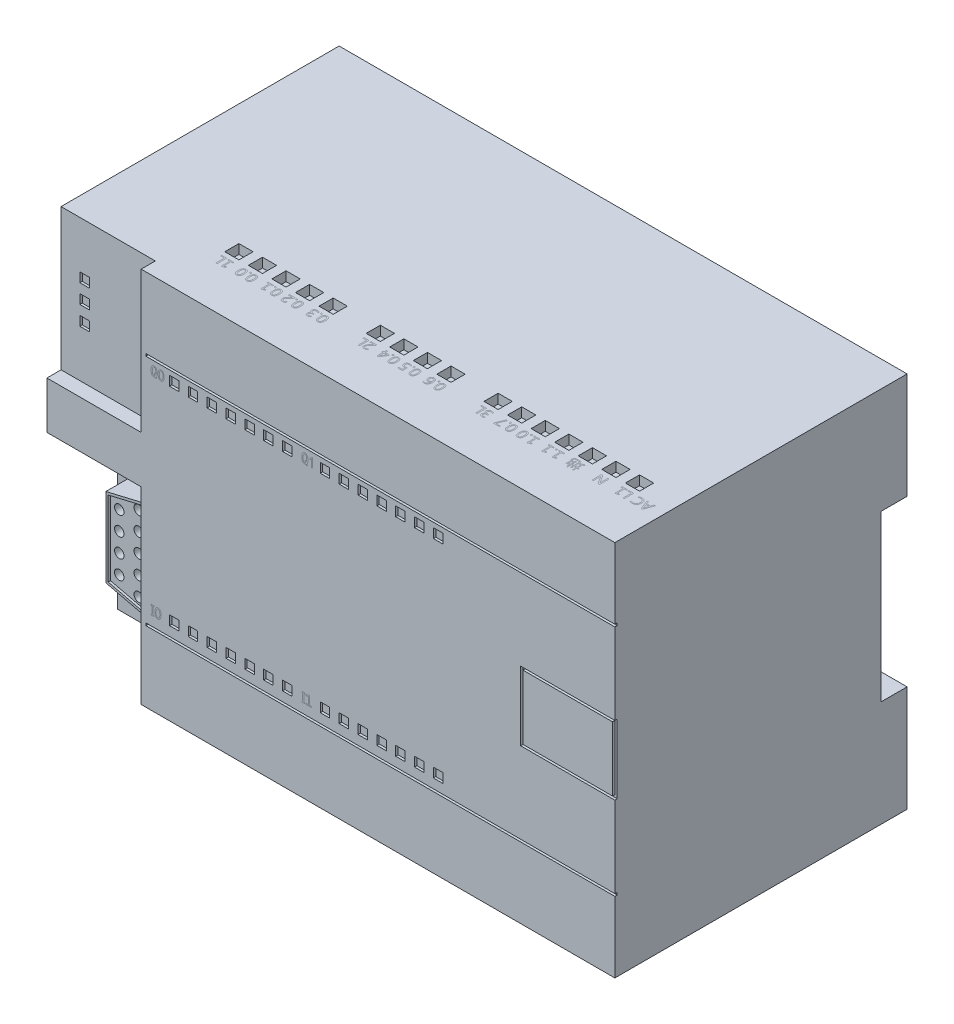
SolidWorks part; units mm, degrees
ref_plane "前视基准面" through (0, 0, 0) normal (0, 0, 1) x (1, 0, 0)
ref_plane "上视基准面" through (0, 0, 0) normal (0, 1, 0) x (1, 0, 0)
ref_plane "右视基准面" through (0, 0, 0) normal (1, 0, 0) x (0, 0, -1)
sketch "草图1" plane through (0, 0, 0) normal (1, 0, 0) x (0, 0, -1)
  line L0 (62, -57.5) -> (62, -80)
  line L1 (0, 0) -> (62, 0)
  line L2 (0, 0) -> (0, -80)
  line L3 (0, -80) -> (62, -80)
  line L4 (62, 0) -> (62, -22.5)
  line L5 (62, -22.5) -> (56.5, -22.5)
  line L7 (62, -57.5) -> (56.5, -57.5)
  line L8 (56.5, -22.5) -> (56.5, -57.5)
  dimension "D1" = 62
  dimension "D2" = 80
  dimension "D3" = 5.5
  dimension "D4" = 35
  dimension "D5" = 22.5
extrude "凸台-拉伸1" add sketch "草图1" along normal blind 120.5
sketch "草图2" plane through (0, 0, 0) normal (0, 0, 1) x (1, 0, 0)
  line L0 (0, -40) -> (120.5, -40) construction
  line L1 (0, 0) -> (0, -80) construction
  line L2 (120.5, 0) -> (120.5, -80) construction
  line L3 (120.5, -80) -> (0, -80) construction
  line L4 (10, -40) -> (10, -80) construction
  line L5 (100.5, -47.3224) -> (120.5, -47.3224)
  line L6 (100.5, -47.3224) -> (100.5, -32.6776)
  line L7 (100.5, -32.6776) -> (120.5, -32.6776)
  line L8 (0, -40) -> (20, -40)
  line L9 (0, -40) -> (0, -80)
  line L10 (0, -80) -> (20, -80)
  line L11 (20, -40) -> (20, -80)
  line L12 (120.5, -47.3224) -> (120.5, -32.6776)
  line L13 (0, 0) -> (20, 0)
  line L14 (0, 0) -> (0, -30)
  line L15 (0, -30) -> (20, -30)
  line L16 (20, 0) -> (20, -30)
  line L17 (101, -46.8224) -> (120, -46.8224)
  line L18 (120, -46.8224) -> (120, -33.1776)
  line L19 (101, -33.1776) -> (120, -33.1776)
  line L20 (101, -46.8224) -> (101, -33.1776)
  line L21 (21, -15) -> (120.5, -15)
  line L22 (21, -15) -> (21, -15.5)
  line L23 (21, -15.5) -> (120.5, -15.5)
  line L24 (120.5, -15) -> (120.5, -15.5)
  line L25 (21, -64.5) -> (120.5, -64.5)
  line L26 (21, -64.5) -> (21, -65)
  line L27 (21, -65) -> (120.5, -65)
  line L28 (120.5, -64.5) -> (120.5, -65)
  line L29 (7, -49.0135) -> (7, -44.0135)
  line L30 (5, -70.9865) -> (7, -70.9865)
  line L31 (5, -70.9865) -> (5, -49.0135)
  line L32 (5, -49.0135) -> (7, -49.0135)
  line L33 (4, -14) -> (6, -14)
  line L34 (4, -10) -> (6, -10)
  line L35 (0, -40) -> (20, -40)
  line L36 (20, -40) -> (20, -80)
  line L37 (0, -60) -> (20, -60) construction
  line L38 (0, -80) -> (20, -80)
  line L39 (0, -40) -> (0, -80)
  line L40 (15, -70.9865) -> (15, -49.0135)
  line L41 (13, -75.9865) -> (7, -75.9865)
  line L42 (13, -75.9865) -> (13, -70.9865)
  line L43 (13, -44.0135) -> (7, -44.0135)
  line L44 (7, -75.9865) -> (7, -70.9865)
  line L45 (13, -49.0135) -> (15, -49.0135)
  line L46 (13, -70.9865) -> (15, -70.9865)
  line L47 (6, -52) -> (6, -68)
  line L48 (6, -52) -> (14, -50.1109)
  line L49 (13, -49.0135) -> (13, -44.0135)
  line L50 (6, -68) -> (14, -69.8891)
  line L51 (7.8503, -58) -> (7.8503, -62) construction
  line L52 (14, -69.8891) -> (14, -50.1109)
  line L53 (120.5, 0) -> (0, 0) construction
  line L54 (30, -60.5) -> (32, -60.5)
  line L55 (26, -60.5) -> (28, -60.5)
  line L56 (26, -60.5) -> (26, -62.5)
  line L57 (26, -62.5) -> (28, -62.5)
  line L58 (28, -60.5) -> (28, -62.5)
  line L59 (30, -60.5) -> (30, -62.5)
  line L60 (30, -62.5) -> (32, -62.5)
  line L61 (32, -60.5) -> (32, -62.5)
  line L62 (34, -60.5) -> (36, -60.5)
  line L63 (34, -60.5) -> (34, -62.5)
  line L64 (34, -62.5) -> (36, -62.5)
  line L65 (36, -60.5) -> (36, -62.5)
  line L66 (38, -60.5) -> (40, -60.5)
  line L67 (38, -60.5) -> (38, -62.5)
  line L68 (38, -62.5) -> (40, -62.5)
  line L69 (40, -60.5) -> (40, -62.5)
  line L70 (42, -60.5) -> (44, -60.5)
  line L71 (42, -60.5) -> (42, -62.5)
  line L72 (42, -62.5) -> (44, -62.5)
  line L73 (44, -60.5) -> (44, -62.5)
  line L74 (46, -60.5) -> (48, -60.5)
  line L75 (46, -60.5) -> (46, -62.5)
  line L76 (46, -62.5) -> (48, -62.5)
  line L77 (48, -60.5) -> (48, -62.5)
  line L78 (50, -60.5) -> (52, -60.5)
  line L79 (50, -60.5) -> (50, -62.5)
  line L80 (50, -62.5) -> (52, -62.5)
  line L81 (52, -60.5) -> (52, -62.5)
  line L82 (4, -10) -> (4, -12)
  line L83 (4, -12) -> (6, -12)
  line L84 (6, -10) -> (6, -12)
  line L85 (4, -14) -> (4, -16)
  line L86 (58, -60.5) -> (60, -60.5)
  line L87 (58, -60.5) -> (58, -62.5)
  line L88 (58, -62.5) -> (60, -62.5)
  line L89 (60, -60.5) -> (60, -62.5)
  line L90 (62, -60.5) -> (64, -60.5)
  line L91 (62, -60.5) -> (62, -62.5)
  line L92 (62, -62.5) -> (64, -62.5)
  line L93 (64, -60.5) -> (64, -62.5)
  line L94 (66, -60.5) -> (68, -60.5)
  line L95 (66, -60.5) -> (66, -62.5)
  line L96 (66, -62.5) -> (68, -62.5)
  line L97 (68, -60.5) -> (68, -62.5)
  line L98 (70, -60.5) -> (72, -60.5)
  line L99 (70, -60.5) -> (70, -62.5)
  line L100 (70, -62.5) -> (72, -62.5)
  line L101 (72, -60.5) -> (72, -62.5)
  line L102 (74, -60.5) -> (76, -60.5)
  line L103 (74, -60.5) -> (74, -62.5)
  line L104 (74, -62.5) -> (76, -62.5)
  line L105 (76, -60.5) -> (76, -62.5)
  line L106 (78, -60.5) -> (80, -60.5)
  line L107 (78, -60.5) -> (78, -62.5)
  line L108 (78, -62.5) -> (80, -62.5)
  line L109 (80, -60.5) -> (80, -62.5)
  line L110 (82, -60.5) -> (84, -60.5)
  line L111 (82, -60.5) -> (82, -62.5)
  line L112 (82, -62.5) -> (84, -62.5)
  line L113 (84, -60.5) -> (84, -62.5)
  line L114 (30, -16.5) -> (32, -16.5)
  line L115 (30, -16.5) -> (30, -18.5)
  line L116 (30, -18.5) -> (32, -18.5)
  line L117 (32, -16.5) -> (32, -18.5)
  line L118 (34, -16.5) -> (36, -16.5)
  line L119 (34, -16.5) -> (34, -18.5)
  line L120 (34, -18.5) -> (36, -18.5)
  line L121 (36, -16.5) -> (36, -18.5)
  line L122 (38, -16.5) -> (40, -16.5)
  line L123 (38, -16.5) -> (38, -18.5)
  line L124 (38, -18.5) -> (40, -18.5)
  line L125 (40, -16.5) -> (40, -18.5)
  line L126 (42, -16.5) -> (44, -16.5)
  line L127 (42, -16.5) -> (42, -18.5)
  line L128 (42, -18.5) -> (44, -18.5)
  line L129 (44, -16.5) -> (44, -18.5)
  line L130 (46, -16.5) -> (48, -16.5)
  line L131 (46, -16.5) -> (46, -18.5)
  line L132 (46, -18.5) -> (48, -18.5)
  line L133 (48, -16.5) -> (48, -18.5)
  line L134 (50, -16.5) -> (52, -16.5)
  line L135 (50, -16.5) -> (50, -18.5)
  line L136 (50, -18.5) -> (52, -18.5)
  line L137 (52, -16.5) -> (52, -18.5)
  line L138 (4, -16) -> (6, -16)
  line L139 (6, -14) -> (6, -16)
  line L140 (4, -18) -> (6, -18)
  line L141 (4, -18) -> (4, -20)
  line L142 (58, -16.5) -> (60, -16.5)
  line L143 (58, -16.5) -> (58, -18.5)
  line L144 (58, -18.5) -> (60, -18.5)
  line L145 (60, -16.5) -> (60, -18.5)
  line L146 (62, -16.5) -> (64, -16.5)
  line L147 (62, -16.5) -> (62, -18.5)
  line L148 (62, -18.5) -> (64, -18.5)
  line L149 (64, -16.5) -> (64, -18.5)
  line L150 (66, -16.5) -> (68, -16.5)
  line L151 (66, -16.5) -> (66, -18.5)
  line L152 (66, -18.5) -> (68, -18.5)
  line L153 (68, -16.5) -> (68, -18.5)
  line L154 (70, -16.5) -> (72, -16.5)
  line L155 (70, -16.5) -> (70, -18.5)
  line L156 (70, -18.5) -> (72, -18.5)
  line L157 (72, -16.5) -> (72, -18.5)
  line L158 (74, -16.5) -> (76, -16.5)
  line L159 (74, -16.5) -> (74, -18.5)
  line L160 (74, -18.5) -> (76, -18.5)
  line L161 (76, -16.5) -> (76, -18.5)
  line L162 (78, -16.5) -> (80, -16.5)
  line L163 (78, -16.5) -> (78, -18.5)
  line L164 (78, -18.5) -> (80, -18.5)
  line L165 (80, -16.5) -> (80, -18.5)
  line L166 (82, -16.5) -> (84, -16.5)
  line L167 (82, -16.5) -> (82, -18.5)
  line L168 (82, -18.5) -> (84, -18.5)
  line L169 (84, -16.5) -> (84, -18.5)
  line L170 (26, -16.5) -> (28, -16.5)
  line L171 (26, -16.5) -> (26, -18.5)
  line L172 (26, -18.5) -> (28, -18.5)
  line L173 (28, -16.5) -> (28, -18.5)
  line L174 (54, -60.5) -> (56, -60.5) [skipped]
  line L175 (54, -60.5) -> (54, -62.5) [skipped]
  line L176 (54, -62.5) -> (56, -62.5) [skipped]
  line L177 (56, -60.5) -> (56, -62.5) [skipped]
  line L178 (54, -16.5) -> (56, -16.5) [skipped]
  line L179 (54, -16.5) -> (54, -18.5) [skipped]
  line L180 (54, -18.5) -> (56, -18.5) [skipped]
  line L181 (56, -16.5) -> (56, -18.5) [skipped]
  line L182 (4, -20) -> (6, -20)
  line L183 (6, -18) -> (6, -20)
  line L184 (5.5, -51.6043) -> (14.5, -49.4791)
  line L185 (14.5, -70.5209) -> (14.5, -49.4791)
  line L186 (5.5, -68.3957) -> (14.5, -70.5209)
  line L187 (5.5, -51.6043) -> (5.5, -68.3957)
  circle A0 centre (10, -47.0135) radius 2
  circle A1 centre (10, -72.9865) radius 2
  circle A2 centre (7.8503, -54) radius 1
  circle A3 centre (7.8503, -58) radius 1
  circle A4 centre (7.8503, -62) radius 1
  circle A5 centre (7.8503, -66) radius 1
  circle A6 centre (11.9798, -52) radius 1
  circle A7 centre (11.9798, -56) radius 1
  circle A8 centre (11.9798, -60) radius 1
  circle A9 centre (11.9798, -64) radius 1
  circle A10 centre (11.9798, -68) radius 1
  point P6 (110.5, -40)
  point P32 (10, -60)
  point P40 (10, -60)
  point P59 (10, -60)
  dimension "D1" = 20
  dimension "D9" = 10
  dimension "D11" = 4
  dimension "D14" = 2
  dimension "D18" = 2
  dimension "D2" = 0.5
  dimension "D3" = 0.5
  dimension "D4" = 1
  dimension "D5" = 20
  dimension "D6" = 10
  dimension "D7" = 5
  dimension "D10" = 5
  dimension "D8" = 2
  dimension "D12" = 3
  dimension "D13" = 16
  dimension "D16" = 4
  dimension "D17" = 2
  dimension "D20" = 4
  dimension "D21" = 15
  dimension "D22" = 15
  dimension "D23" = 2
  dimension "D24" = 2
  dimension "D25" = 2
  dimension "D26" = 5
  dimension "D30" = 2
  dimension "D31" = 2
  dimension "D33" = 10
  dimension "D34" = 4
  dimension "D29" = 0.5
  dimension "D35" = 0.5
  dimension "D15" = 4
  dimension "D19" = 5
  dimension "D27" = 15
  dimension "D28" = 2
  dimension "D32" = 3
extrude "切除-拉伸1" cut sketch "草图2" against normal blind 15 contours L11 L10 L9 L8 | L40 L45 L49 L43 L29 L32 L31 L30 L44 L41 L42 L46
extrude "切除-拉伸2" cut sketch "草图2<4>" against normal blind 0.5 contours L27 L28 L25 L26 | L23 L24 L21 L22 | L6 L7 L12 L5 | L20 L19 L18 L17 | L172 L173 L170 L171 | L116 L117 L114 L115 | L120 L121 L118 L119 | L124 L125 L122 L123 | L128 L129 L126 L127 | L132 L133 L130 L131 | L136 L137 L134 L135 | L144 L145 L142 L143 | L148 L149 L146 L147 | L152 L153 L150 L151 | L156 L157 L154 L155 | L160 L161 L158 L159 | L164 L165 L162 L163 | L168 L169 L166 L167 | L112 L113 L110 L111 | L108 L109 L106 L107 | L104 L105 L102 L103 | L100 L101 L98 L99 | L96 L97 L94 L95 | L92 L93 L90 L91 | L88 L89 L86 L87 | L80 L81 L78 L79 | L76 L77 L74 L75 | L72 L73 L70 L71 | L68 L69 L66 L67 | L64 L65 L62 L63 | L60 L61 L54 L59 | L57 L58 L55 L56
sketch "草图2<4>" plane through (0, 0, 0) normal (0, 0, 1) x (1, 0, 0) same geometry as "草图2"
extrude "切除-拉伸3" cut sketch "草图2<5>" against normal blind 3 contours L16 L15 L14 L13
sketch "草图2<5>" plane through (0, 0, 0) normal (0, 0, 1) x (1, 0, 0) same geometry as "草图2"
extrude "切除-拉伸4" cut sketch "草图2<6>" against normal blind 3.5 contours L83 L84 L34 L82 | L138 L139 L33 L85 | L182 L183 L140 L141
sketch "草图2<6>" plane through (0, 0, 0) normal (0, 0, 1) x (1, 0, 0) same geometry as "草图2"
extrude "切除-拉伸5" cut sketch "草图2<7>" against normal blind 13 contours L29 L43 L49 L45 L40 L46 L42 L41 L44 L30 L31 L32 | L187 L186 L185 L184
sketch "草图2<7>" plane through (0, 0, 0) normal (0, 0, 1) x (1, 0, 0) same geometry as "草图2"
extrude "切除-拉伸6" cut sketch "草图2<8>" against normal blind 15 contours A0 | A1
sketch "草图2<8>" plane through (0, 0, 0) normal (0, 0, 1) x (1, 0, 0) same geometry as "草图2"
extrude "切除-拉伸7" cut sketch "草图2<9>" against normal blind 15 contours A2 | A3 | A4 | A5 | A9 | A10 | A8 | A7 | A6
sketch "草图2<9>" plane through (0, 0, 0) normal (0, 0, 1) x (1, 0, 0) same geometry as "草图2"
extrude "切除-拉伸8" cut sketch "草图2<10>" against normal blind 7.5 contours L47 L50 L52 L48
sketch "草图2<10>" plane through (0, 0, 0) normal (0, 0, 1) x (1, 0, 0) same geometry as "草图2"
sketch "草图3" plane through (0, 0, 0) normal (0, 0, 1) x (1, 0, 0)
  line L0 (22, -18.5) -> (24, -18.5) construction
  line L1 (54, -18.5) -> (56, -18.5) construction
  line L2 (26, -16.5) -> (26, -18.5) construction
  line L4 (26, -18.5) -> (28, -18.5) construction
  line L5 (50, -18.5) -> (52, -18.5) construction
  line L6 (20, -40) -> (100.5, -40) construction
  line L7 (100.5, -47.3224) -> (100.5, -32.6776) construction
  line L8 (22, -62.5) -> (24, -62.5) construction
  line L9 (54, -62.5) -> (56, -62.5) construction
  line L10 (26, -60.5) -> (26, -62.5) construction
  line L11 (52, -60.5) -> (52, -62.5) construction
  line L12 (26, -62.5) -> (28, -62.5) construction
  line L13 (50, -62.5) -> (52, -62.5) construction
  text T0 "Q0" font "黑体" height 2
  text T1 "Q1" font "黑体" height 2
  text T2 "I0\r\n" font "微软雅黑" height 2
  text T3 "I1" font "微软雅黑" height 2
  dimension "D1" = 2
  dimension "D2" = 2
  dimension "D3" = 2
  dimension "D4" = 2
  dimension "D5" = 2
  dimension "D6" = 2
  dimension "D7" = 2
  dimension "D8" = 2
wrap "包覆1" sketch "草图3" wrap type scribe source sketch "草图3" face at (27, -17.5, 0)
extrude "切除-拉伸9" cut sketch "草图2<11>" against normal blind 7 contours L187 L186 L185 L184
sketch "草图2<11>" plane through (0, 0, 0) normal (0, 0, 1) x (1, 0, 0) same geometry as "草图2"
sketch "草图4" plane through (0, -80, 0) normal (0, -1, 0) x (1, 0, 0)
  line L0 (30.6688, -15.0662) -> (33.6688, -15.0662)
  line L1 (25.6688, -15.0662) -> (28.6688, -15.0662)
  line L2 (25.6688, -15.0662) -> (25.6688, -12.0662)
  line L3 (25.6688, -12.0662) -> (28.6688, -12.0662)
  line L4 (28.6688, -15.0662) -> (28.6688, -12.0662)
  line L5 (30.6688, -15.0662) -> (30.6688, -12.0662)
  line L6 (30.6688, -12.0662) -> (33.6688, -12.0662)
  line L7 (33.6688, -15.0662) -> (33.6688, -12.0662)
  line L8 (35.6688, -15.0662) -> (38.6688, -15.0662)
  line L9 (35.6688, -15.0662) -> (35.6688, -12.0662)
  line L10 (35.6688, -12.0662) -> (38.6688, -12.0662)
  line L11 (38.6688, -15.0662) -> (38.6688, -12.0662)
  line L12 (40.6688, -15.0662) -> (43.6688, -15.0662)
  line L13 (40.6688, -15.0662) -> (40.6688, -12.0662)
  line L14 (40.6688, -12.0662) -> (43.6688, -12.0662)
  line L15 (43.6688, -15.0662) -> (43.6688, -12.0662)
  line L16 (45.6688, -15.0662) -> (48.6688, -15.0662)
  line L17 (45.6688, -15.0662) -> (45.6688, -12.0662)
  line L18 (45.6688, -12.0662) -> (48.6688, -12.0662)
  line L19 (48.6688, -15.0662) -> (48.6688, -12.0662)
  line L20 (50.6688, -15.0662) -> (53.6688, -15.0662)
  line L21 (50.6688, -15.0662) -> (50.6688, -12.0662)
  line L22 (50.6688, -12.0662) -> (53.6688, -12.0662)
  line L23 (53.6688, -15.0662) -> (53.6688, -12.0662)
  line L24 (55.6688, -15.0662) -> (58.6688, -15.0662)
  line L25 (55.6688, -15.0662) -> (55.6688, -12.0662)
  line L26 (55.6688, -12.0662) -> (58.6688, -12.0662)
  line L27 (58.6688, -15.0662) -> (58.6688, -12.0662)
  line L28 (60.6688, -15.0662) -> (63.6688, -15.0662)
  line L29 (60.6688, -15.0662) -> (60.6688, -12.0662)
  line L30 (60.6688, -12.0662) -> (63.6688, -12.0662)
  line L31 (63.6688, -15.0662) -> (63.6688, -12.0662)
  line L32 (65.6688, -15.0662) -> (68.6688, -15.0662)
  line L33 (65.6688, -15.0662) -> (65.6688, -12.0662)
  line L34 (65.6688, -12.0662) -> (68.6688, -12.0662)
  line L35 (68.6688, -15.0662) -> (68.6688, -12.0662)
  line L36 (70.6688, -15.0662) -> (73.6688, -15.0662)
  line L37 (70.6688, -15.0662) -> (70.6688, -12.0662)
  line L38 (70.6688, -12.0662) -> (73.6688, -12.0662)
  line L39 (73.6688, -15.0662) -> (73.6688, -12.0662)
  line L40 (75.6688, -15.0662) -> (78.6688, -15.0662)
  line L41 (75.6688, -15.0662) -> (75.6688, -12.0662)
  line L42 (75.6688, -12.0662) -> (78.6688, -12.0662)
  line L43 (78.6688, -15.0662) -> (78.6688, -12.0662)
  line L44 (80.6688, -15.0662) -> (83.6688, -15.0662)
  line L45 (80.6688, -15.0662) -> (80.6688, -12.0662)
  line L46 (80.6688, -12.0662) -> (83.6688, -12.0662)
  line L47 (83.6688, -15.0662) -> (83.6688, -12.0662)
  line L48 (85.6688, -15.0662) -> (88.6688, -15.0662)
  line L49 (85.6688, -15.0662) -> (85.6688, -12.0662)
  line L50 (85.6688, -12.0662) -> (88.6688, -12.0662)
  line L51 (88.6688, -15.0662) -> (88.6688, -12.0662)
  line L52 (90.6688, -15.0662) -> (93.6688, -15.0662)
  line L53 (90.6688, -15.0662) -> (90.6688, -12.0662)
  line L54 (90.6688, -12.0662) -> (93.6688, -12.0662)
  line L55 (93.6688, -15.0662) -> (93.6688, -12.0662)
  line L56 (95.6688, -15.0662) -> (98.6688, -15.0662)
  line L57 (95.6688, -15.0662) -> (95.6688, -12.0662)
  line L58 (95.6688, -12.0662) -> (98.6688, -12.0662)
  line L59 (98.6688, -15.0662) -> (98.6688, -12.0662)
  line L60 (100.6688, -15.0662) -> (103.6688, -15.0662)
  line L61 (100.6688, -15.0662) -> (100.6688, -12.0662)
  line L62 (100.6688, -12.0662) -> (103.6688, -12.0662)
  line L63 (103.6688, -15.0662) -> (103.6688, -12.0662)
  line L64 (105.6688, -15.0662) -> (108.6688, -15.0662)
  line L65 (105.6688, -15.0662) -> (105.6688, -12.0662)
  line L66 (105.6688, -12.0662) -> (108.6688, -12.0662)
  line L67 (108.6688, -15.0662) -> (108.6688, -12.0662)
  line L68 (110.6688, -15.0662) -> (113.6688, -15.0662)
  line L69 (110.6688, -15.0662) -> (110.6688, -12.0662)
  line L70 (110.6688, -12.0662) -> (113.6688, -12.0662)
  line L71 (113.6688, -15.0662) -> (113.6688, -12.0662)
  dimension "D1" = 3
  dimension "D2" = 3
  dimension "D3" = 18
extrude "切除-拉伸10" cut sketch "草图4" against normal blind 2
sketch "草图5" plane through (0, 0, 0) normal (0, 1, 0) x (1, 0, 0)
  line L0 (25.6688, 12.0662) -> (25.6688, 15.0662) construction
  line L1 (25.6688, 15.0662) -> (28.6688, 15.0662) construction
  line L2 (28.6688, 15.0662) -> (28.6688, 12.0662) construction
  line L3 (28.6688, 12.0662) -> (25.6688, 12.0662) construction
  line L4 (30.6688, 12.0662) -> (30.6688, 15.0662) construction
  line L5 (30.6688, 15.0662) -> (33.6688, 15.0662) construction
  line L6 (33.6688, 15.0662) -> (33.6688, 12.0662) construction
  line L7 (33.6688, 12.0662) -> (30.6688, 12.0662) construction
  line L8 (35.6688, 12.0662) -> (35.6688, 15.0662) construction
  line L9 (35.6688, 15.0662) -> (38.6688, 15.0662) construction
  line L10 (38.6688, 15.0662) -> (38.6688, 12.0662) construction
  line L11 (38.6688, 12.0662) -> (35.6688, 12.0662) construction
  line L12 (40.6688, 12.0662) -> (40.6688, 15.0662) construction
  line L13 (40.6688, 15.0662) -> (43.6688, 15.0662) construction
  line L14 (43.6688, 15.0662) -> (43.6688, 12.0662) construction
  line L15 (43.6688, 12.0662) -> (40.6688, 12.0662) construction
  line L16 (45.6688, 12.0662) -> (45.6688, 15.0662) construction
  line L17 (45.6688, 15.0662) -> (48.6688, 15.0662) construction
  line L18 (48.6688, 15.0662) -> (48.6688, 12.0662) construction
  line L19 (48.6688, 12.0662) -> (45.6688, 12.0662) construction
  line L20 (55.6688, 12.0662) -> (55.6688, 15.0662) construction
  line L21 (55.6688, 15.0662) -> (58.6688, 15.0662) construction
  line L22 (58.6688, 15.0662) -> (58.6688, 12.0662) construction
  line L23 (58.6688, 12.0662) -> (55.6688, 12.0662) construction
  line L24 (60.6688, 12.0662) -> (60.6688, 15.0662) construction
  line L25 (60.6688, 15.0662) -> (63.6688, 15.0662) construction
  line L26 (63.6688, 15.0662) -> (63.6688, 12.0662) construction
  line L27 (63.6688, 12.0662) -> (60.6688, 12.0662) construction
  line L28 (65.6688, 12.0662) -> (65.6688, 15.0662) construction
  line L29 (65.6688, 15.0662) -> (68.6688, 15.0662) construction
  line L30 (68.6688, 15.0662) -> (68.6688, 12.0662) construction
  line L31 (68.6688, 12.0662) -> (65.6688, 12.0662) construction
  line L32 (70.6688, 12.0662) -> (70.6688, 15.0662) construction
  line L33 (70.6688, 15.0662) -> (73.6688, 15.0662) construction
  line L34 (73.6688, 15.0662) -> (73.6688, 12.0662) construction
  line L35 (73.6688, 12.0662) -> (70.6688, 12.0662) construction
  line L36 (80.6688, 12.0662) -> (80.6688, 15.0662) construction
  line L37 (80.6688, 15.0662) -> (83.6688, 15.0662) construction
  line L38 (83.6688, 15.0662) -> (83.6688, 12.0662) construction
  line L39 (83.6688, 12.0662) -> (80.6688, 12.0662) construction
  line L40 (85.6688, 12.0662) -> (85.6688, 15.0662) construction
  line L41 (85.6688, 15.0662) -> (88.6688, 15.0662) construction
  line L42 (88.6688, 15.0662) -> (88.6688, 12.0662) construction
  line L43 (88.6688, 12.0662) -> (85.6688, 12.0662) construction
  line L44 (90.6688, 12.0662) -> (90.6688, 15.0662) construction
  line L45 (90.6688, 15.0662) -> (93.6688, 15.0662) construction
  line L46 (93.6688, 15.0662) -> (93.6688, 12.0662) construction
  line L47 (93.6688, 12.0662) -> (90.6688, 12.0662) construction
  line L48 (95.6688, 12.0662) -> (95.6688, 15.0662) construction
  line L49 (95.6688, 15.0662) -> (98.6688, 15.0662) construction
  line L50 (98.6688, 15.0662) -> (98.6688, 12.0662) construction
  line L51 (98.6688, 12.0662) -> (95.6688, 12.0662) construction
  line L52 (100.6688, 12.0662) -> (100.6688, 15.0662) construction
  line L53 (100.6688, 15.0662) -> (103.6688, 15.0662) construction
  line L54 (103.6688, 15.0662) -> (103.6688, 12.0662) construction
  line L55 (103.6688, 12.0662) -> (100.6688, 12.0662) construction
  line L56 (105.6688, 12.0662) -> (105.6688, 15.0662) construction
  line L57 (105.6688, 15.0662) -> (108.6688, 15.0662) construction
  line L58 (108.6688, 15.0662) -> (108.6688, 12.0662) construction
  line L59 (108.6688, 12.0662) -> (105.6688, 12.0662) construction
  line L60 (110.6688, 12.0662) -> (110.6688, 15.0662) construction
  line L61 (110.6688, 15.0662) -> (113.6688, 15.0662) construction
  line L62 (113.6688, 15.0662) -> (113.6688, 12.0662) construction
  line L63 (113.6688, 12.0662) -> (110.6688, 12.0662) construction
  line L64 (25.6688, 12.0662) -> (25.6688, 15.0662)
  line L65 (25.6688, 15.0662) -> (28.6688, 15.0662)
  line L66 (28.6688, 15.0662) -> (28.6688, 12.0662)
  line L67 (28.6688, 12.0662) -> (25.6688, 12.0662)
  line L68 (30.6688, 12.0662) -> (30.6688, 15.0662)
  line L69 (30.6688, 15.0662) -> (33.6688, 15.0662)
  line L70 (33.6688, 15.0662) -> (33.6688, 12.0662)
  line L71 (33.6688, 12.0662) -> (30.6688, 12.0662)
  line L72 (35.6688, 12.0662) -> (35.6688, 15.0662)
  line L73 (35.6688, 15.0662) -> (38.6688, 15.0662)
  line L74 (38.6688, 15.0662) -> (38.6688, 12.0662)
  line L75 (38.6688, 12.0662) -> (35.6688, 12.0662)
  line L76 (40.6688, 12.0662) -> (40.6688, 15.0662)
  line L77 (40.6688, 15.0662) -> (43.6688, 15.0662)
  line L78 (43.6688, 15.0662) -> (43.6688, 12.0662)
  line L79 (43.6688, 12.0662) -> (40.6688, 12.0662)
  line L80 (45.6688, 12.0662) -> (45.6688, 15.0662)
  line L81 (45.6688, 15.0662) -> (48.6688, 15.0662)
  line L82 (48.6688, 15.0662) -> (48.6688, 12.0662)
  line L83 (48.6688, 12.0662) -> (45.6688, 12.0662)
  line L84 (55.6688, 12.0662) -> (55.6688, 15.0662)
  line L85 (55.6688, 15.0662) -> (58.6688, 15.0662)
  line L86 (58.6688, 15.0662) -> (58.6688, 12.0662)
  line L87 (58.6688, 12.0662) -> (55.6688, 12.0662)
  line L88 (60.6688, 12.0662) -> (60.6688, 15.0662)
  line L89 (60.6688, 15.0662) -> (63.6688, 15.0662)
  line L90 (63.6688, 15.0662) -> (63.6688, 12.0662)
  line L91 (63.6688, 12.0662) -> (60.6688, 12.0662)
  line L92 (65.6688, 12.0662) -> (65.6688, 15.0662)
  line L93 (65.6688, 15.0662) -> (68.6688, 15.0662)
  line L94 (68.6688, 15.0662) -> (68.6688, 12.0662)
  line L95 (68.6688, 12.0662) -> (65.6688, 12.0662)
  line L96 (70.6688, 12.0662) -> (70.6688, 15.0662)
  line L97 (70.6688, 15.0662) -> (73.6688, 15.0662)
  line L98 (73.6688, 15.0662) -> (73.6688, 12.0662)
  line L99 (73.6688, 12.0662) -> (70.6688, 12.0662)
  line L100 (80.6688, 12.0662) -> (80.6688, 15.0662)
  line L101 (80.6688, 15.0662) -> (83.6688, 15.0662)
  line L102 (83.6688, 15.0662) -> (83.6688, 12.0662)
  line L103 (83.6688, 12.0662) -> (80.6688, 12.0662)
  line L104 (85.6688, 12.0662) -> (85.6688, 15.0662)
  line L105 (85.6688, 15.0662) -> (88.6688, 15.0662)
  line L106 (88.6688, 15.0662) -> (88.6688, 12.0662)
  line L107 (88.6688, 12.0662) -> (85.6688, 12.0662)
  line L108 (90.6688, 12.0662) -> (90.6688, 15.0662)
  line L109 (90.6688, 15.0662) -> (93.6688, 15.0662)
  line L110 (93.6688, 15.0662) -> (93.6688, 12.0662)
  line L111 (93.6688, 12.0662) -> (90.6688, 12.0662)
  line L112 (95.6688, 12.0662) -> (95.6688, 15.0662)
  line L113 (95.6688, 15.0662) -> (98.6688, 15.0662)
  line L114 (98.6688, 15.0662) -> (98.6688, 12.0662)
  line L115 (98.6688, 12.0662) -> (95.6688, 12.0662)
  line L116 (100.6688, 12.0662) -> (100.6688, 15.0662)
  line L117 (100.6688, 15.0662) -> (103.6688, 15.0662)
  line L118 (103.6688, 15.0662) -> (103.6688, 12.0662)
  line L119 (103.6688, 12.0662) -> (100.6688, 12.0662)
  line L120 (105.6688, 12.0662) -> (105.6688, 15.0662)
  line L121 (105.6688, 15.0662) -> (108.6688, 15.0662)
  line L122 (108.6688, 15.0662) -> (108.6688, 12.0662)
  line L123 (108.6688, 12.0662) -> (105.6688, 12.0662)
  line L124 (110.6688, 12.0662) -> (110.6688, 15.0662)
  line L125 (110.6688, 15.0662) -> (113.6688, 15.0662)
  line L126 (113.6688, 15.0662) -> (113.6688, 12.0662)
  line L127 (113.6688, 12.0662) -> (110.6688, 12.0662)
extrude "切除-拉伸11" cut sketch "草图5" against normal blind 2
sketch "草图6" plane through (0, -80, 0) normal (0, -1, 0) x (1, 0, 0)
  line L0 (25.6688, -11.0662) -> (113.7494, -11.0662) construction
  line L1 (28.6688, -12.0662) -> (25.6688, -12.0662) construction
  text T0 "1M 0.0 0.1  0.2  0.3 0.4  0.5  0.6  0.7 2M 1.0  1.1  1.2 1.3 1.4  1.5   M  L+" font "微软雅黑" height 2
  dimension "D1" = 1
wrap "包覆2" sketch "草图6" wrap type scribe source sketch "草图6" face at (112.1688, -80, -13.5662)
sketch "草图7" plane through (0, 0, 0) normal (0, 1, 0) x (1, 0, 0)
  line L0 (118.0812, 11.0662) -> (25.7314, 11.0662) construction
  line L1 (25.6688, 12.0662) -> (28.6688, 12.0662) construction
  text T0 "AC L1   N    地  1.1  1.0 0.7  3L         0.6  0.5 0.4  2L         0.3  0.2 0.1  0.0  1L" font "微软雅黑" height 2
  dimension "D1" = 1
wrap "包覆3" sketch "草图7" wrap type scribe source sketch "草图7" face at (112.1688, 0, -13.5662)
sketch "0_0_Point" plane through (0, -2, 0) normal (0, 1, 0) x (1, 0, 0)
  line L0 (113.6688, 12.0662) -> (113.6688, 15.0662) construction
  line L1 (110.6688, 12.0662) -> (113.6688, 12.0662) construction
  point P0 (112.1688, 13.5662)
  dimension "D1" = 1.5
  dimension "D2" = 1.5
other "0_0" parameters "直径"=2, "端头长度"=2
ref_axis "基准轴1" through (112.1688, 8, -13.5662) along (0, -1, 0)
sketch "1_0_Point" plane through (0, -2, 0) normal (0, 1, 0) x (1, 0, 0)
  line L0 (105.6688, 12.0662) -> (108.6688, 12.0662) construction
  line L1 (108.6688, 12.0662) -> (108.6688, 15.0662) construction
  point P0 (107.1688, 13.5662)
  dimension "D1" = 1.5
  dimension "D2" = 1.5
other "1_0" parameters "直径"=2, "端头长度"=2
ref_axis "基准轴2" through (107.1688, 8, -13.5662) along (0, -1, 0)
sketch "2_0_Point" plane through (0, -2, 0) normal (0, 1, 0) x (1, 0, 0)
  line L0 (100.6688, 12.0662) -> (103.6688, 12.0662) construction
  line L1 (103.6688, 12.0662) -> (103.6688, 15.0662) construction
  point P0 (102.1688, 13.5662)
  dimension "D1" = 1.5
  dimension "D2" = 1.5
other "2_0" parameters "直径"=2, "端头长度"=2
ref_axis "基准轴3" through (102.1688, 8, -13.5662) along (0, -1, 0)
sketch "3_0_Point" plane through (0, -2, 0) normal (0, 1, 0) x (1, 0, 0)
  line L0 (25.6688, 12.0662) -> (28.6688, 12.0662) construction
  line L1 (28.6688, 12.0662) -> (28.6688, 15.0662) construction
  point P0 (27.1688, 13.5662)
  dimension "D1" = 1.5
  dimension "D2" = 1.5
other "3_0" parameters "直径"=2, "端头长度"=2
ref_axis "基准轴4" through (27.1688, 8, -13.5662) along (0, -1, 0)
sketch "4_0_Point" plane through (0, -2, 0) normal (0, 1, 0) x (1, 0, 0)
  line L0 (30.6688, 12.0662) -> (33.6688, 12.0662) construction
  line L1 (33.6688, 12.0662) -> (33.6688, 15.0662) construction
  point P0 (32.1688, 13.5662)
  dimension "D1" = 1.5
  dimension "D2" = 1.5
other "4_0" parameters "直径"=2, "端头长度"=2
ref_axis "基准轴5" through (32.1688, 8, -13.5662) along (0, -1, 0)
sketch "5_0_Point" plane through (0, -2, 0) normal (0, 1, 0) x (1, 0, 0)
  line L0 (35.6688, 12.0662) -> (38.6688, 12.0662) construction
  line L1 (38.6688, 12.0662) -> (38.6688, 15.0662) construction
  point P0 (37.1688, 13.5662)
  dimension "D1" = 1.5
  dimension "D2" = 1.5
other "5_0" parameters "直径"=2, "端头长度"=2
ref_axis "基准轴6" through (37.1688, 8, -13.5662) along (0, -1, 0)
sketch "6_0_Point" plane through (0, -2, 0) normal (0, 1, 0) x (1, 0, 0)
  line L0 (40.6688, 12.0662) -> (43.6688, 12.0662) construction
  line L1 (43.6688, 12.0662) -> (43.6688, 15.0662) construction
  point P0 (42.1688, 13.5662)
  dimension "D1" = 1.5
  dimension "D2" = 1.5
other "6_0" parameters "直径"=2, "端头长度"=2
ref_axis "基准轴7" through (42.1688, 8, -13.5662) along (0, -1, 0)
sketch "7_0_Point" plane through (0, -2, 0) normal (0, 1, 0) x (1, 0, 0)
  line L0 (45.6688, 12.0662) -> (48.6688, 12.0662) construction
  line L1 (48.6688, 12.0662) -> (48.6688, 15.0662) construction
  point P0 (47.1688, 13.5662)
  dimension "D1" = 1.5
  dimension "D2" = 1.5
other "7_0" parameters "直径"=2, "端头长度"=2
ref_axis "基准轴8" through (47.1688, 8, -13.5662) along (0, -1, 0)
sketch "8_0_Point" plane through (0, -2, 0) normal (0, 1, 0) x (1, 0, 0)
  line L0 (55.6688, 12.0662) -> (58.6688, 12.0662) construction
  line L1 (58.6688, 12.0662) -> (58.6688, 15.0662) construction
  point P0 (57.1688, 13.5662)
  dimension "D1" = 1.5
  dimension "D2" = 1.5
other "8_0" parameters "直径"=2, "端头长度"=2
ref_axis "基准轴9" through (57.1688, 8, -13.5662) along (0, -1, 0)
sketch "9_0_Point" plane through (0, -2, 0) normal (0, 1, 0) x (1, 0, 0)
  line L0 (60.6688, 12.0662) -> (63.6688, 12.0662) construction
  line L1 (63.6688, 12.0662) -> (63.6688, 15.0662) construction
  point P0 (62.1688, 13.5662)
  dimension "D1" = 1.5
  dimension "D2" = 1.5
other "9_0" parameters "直径"=2, "端头长度"=2
ref_axis "基准轴10" through (62.1688, 8, -13.5662) along (0, -1, 0)
sketch "10_0_Point" plane through (0, -2, 0) normal (0, 1, 0) x (1, 0, 0)
  line L0 (65.6688, 12.0662) -> (68.6688, 12.0662) construction
  line L1 (68.6688, 12.0662) -> (68.6688, 15.0662) construction
  point P0 (67.1688, 13.5662)
  dimension "D1" = 1.5
  dimension "D2" = 1.5
other "10_0" parameters "直径"=2, "端头长度"=2
ref_axis "基准轴11" through (67.1688, 8, -13.5662) along (0, -1, 0)
sketch "11_0_Point" plane through (0, -2, 0) normal (0, 1, 0) x (1, 0, 0)
  line L0 (70.6688, 12.0662) -> (73.6688, 12.0662) construction
  line L1 (73.6688, 12.0662) -> (73.6688, 15.0662) construction
  point P0 (72.1688, 13.5662)
  dimension "D1" = 1.5
  dimension "D2" = 1.5
other "11_0" parameters "直径"=2, "端头长度"=2
ref_axis "基准轴12" through (72.1688, 8, -13.5662) along (0, -1, 0)
sketch "12_0_Point" plane through (0, -2, 0) normal (0, 1, 0) x (1, 0, 0)
  line L0 (80.6688, 12.0662) -> (83.6688, 12.0662) construction
  line L1 (83.6688, 12.0662) -> (83.6688, 15.0662) construction
  point P0 (82.1688, 13.5662)
  dimension "D1" = 1.5
  dimension "D2" = 1.5
other "12_0" parameters "直径"=2, "端头长度"=2
ref_axis "基准轴13" through (82.1688, 8, -13.5662) along (0, -1, 0)
sketch "13_0_Point" plane through (0, -2, 0) normal (0, 1, 0) x (1, 0, 0)
  line L0 (85.6688, 12.0662) -> (88.6688, 12.0662) construction
  line L1 (88.6688, 12.0662) -> (88.6688, 15.0662) construction
  point P0 (87.1688, 13.5662)
  dimension "D1" = 1.5
  dimension "D2" = 1.5
other "13_0" parameters "直径"=2, "端头长度"=2
ref_axis "基准轴14" through (87.1688, 8, -13.5662) along (0, -1, 0)
sketch "14_0_Point" plane through (0, -2, 0) normal (0, 1, 0) x (1, 0, 0)
  line L0 (90.6688, 12.0662) -> (93.6688, 12.0662) construction
  line L1 (93.6688, 12.0662) -> (93.6688, 15.0662) construction
  point P0 (92.1688, 13.5662)
  dimension "D1" = 1.5
  dimension "D2" = 1.5
other "14_0" parameters "直径"=2, "端头长度"=2
ref_axis "基准轴15" through (92.1688, 8, -13.5662) along (0, -1, 0)
sketch "15_0_Point" plane through (0, -2, 0) normal (0, 1, 0) x (1, 0, 0)
  line L0 (95.6688, 12.0662) -> (98.6688, 12.0662) construction
  line L1 (98.6688, 12.0662) -> (98.6688, 15.0662) construction
  point P0 (97.1688, 13.5662)
  dimension "D1" = 1.5
  dimension "D2" = 1.5
other "15_0" parameters "直径"=2, "端头长度"=2
ref_axis "基准轴16" through (97.1688, 8, -13.5662) along (0, -1, 0)
sketch "16_0_Point" plane through (0, -78, 0) normal (0, -1, 0) x (1, 0, 0)
  line L0 (28.6688, -12.0662) -> (25.6688, -12.0662) construction
  line L1 (25.6688, -12.0662) -> (25.6688, -15.0662) construction
  point P0 (27.1688, -13.5662)
  dimension "D1" = 1.5
  dimension "D2" = 1.5
other "16_0" parameters "直径"=2, "端头长度"=2
ref_axis "基准轴17" through (27.1688, -88, -13.5662) along (0, 1, 0)
sketch "17_0_Point" plane through (0, -78, 0) normal (0, -1, 0) x (1, 0, 0)
  line L0 (33.6688, -12.0662) -> (30.6688, -12.0662) construction
  line L1 (30.6688, -12.0662) -> (30.6688, -15.0662) construction
  point P0 (32.1688, -13.5662)
  dimension "D1" = 1.5
  dimension "D2" = 1.5
other "17_0" parameters "直径"=2, "端头长度"=2
ref_axis "基准轴18" through (32.1688, -88, -13.5662) along (0, 1, 0)
sketch "18_0_Point" plane through (0, -78, 0) normal (0, -1, 0) x (1, 0, 0)
  line L0 (38.6688, -12.0662) -> (35.6688, -12.0662) construction
  line L1 (35.6688, -12.0662) -> (35.6688, -15.0662) construction
  point P0 (37.1688, -13.5662)
  dimension "D1" = 1.5
  dimension "D2" = 1.5
other "18_0" parameters "直径"=2, "端头长度"=2
ref_axis "基准轴19" through (37.1688, -88, -13.5662) along (0, 1, 0)
sketch "19_0_Point" plane through (0, -78, 0) normal (0, -1, 0) x (1, 0, 0)
  line L0 (43.6688, -12.0662) -> (40.6688, -12.0662) construction
  line L1 (40.6688, -12.0662) -> (40.6688, -15.0662) construction
  point P0 (42.1688, -13.5662)
  dimension "D1" = 1.5
  dimension "D2" = 1.5
other "19_0" parameters "直径"=2, "端头长度"=2
ref_axis "基准轴35" through (42.1688, -88, -13.5662) along (0, 1, 0)
sketch "20_0_Point" plane through (0, -78, 0) normal (0, -1, 0) x (1, 0, 0)
  line L0 (48.6688, -12.0662) -> (45.6688, -12.0662) construction
  line L1 (45.6688, -12.0662) -> (45.6688, -15.0662) construction
  point P0 (47.1688, -13.5662)
  dimension "D1" = 1.5
  dimension "D2" = 1.5
other "20_0" parameters "直径"=2, "端头长度"=2
ref_axis "基准轴36" through (47.1688, -88, -13.5662) along (0, 1, 0)
sketch "21_0_Point" plane through (0, -78, 0) normal (0, -1, 0) x (1, 0, 0)
  line L0 (53.6688, -12.0662) -> (50.6688, -12.0662) construction
  line L1 (50.6688, -12.0662) -> (50.6688, -15.0662) construction
  point P0 (52.1688, -13.5662)
  dimension "D1" = 1.5
  dimension "D2" = 1.5
other "21_0" parameters "直径"=2, "端头长度"=2
ref_axis "基准轴37" through (52.1688, -88, -13.5662) along (0, 1, 0)
sketch "22_0_Point" plane through (0, -78, 0) normal (0, -1, 0) x (1, 0, 0)
  line L0 (58.6688, -12.0662) -> (55.6688, -12.0662) construction
  line L1 (55.6688, -12.0662) -> (55.6688, -15.0662) construction
  point P0 (57.1688, -13.5662)
  dimension "D1" = 1.5
  dimension "D2" = 1.5
other "22_0" parameters "直径"=2, "端头长度"=2
ref_axis "基准轴38" through (57.1688, -88, -13.5662) along (0, 1, 0)
sketch "23_0_Point" plane through (0, -78, 0) normal (0, -1, 0) x (1, 0, 0)
  line L0 (63.6688, -12.0662) -> (60.6688, -12.0662) construction
  line L1 (60.6688, -12.0662) -> (60.6688, -15.0662) construction
  point P0 (62.1688, -13.5662)
  dimension "D1" = 1.5
  dimension "D2" = 1.5
other "23_0" parameters "直径"=2, "端头长度"=2
ref_axis "基准轴39" through (62.1688, -88, -13.5662) along (0, 1, 0)
sketch "24_0_Point" plane through (0, -78, 0) normal (0, -1, 0) x (1, 0, 0)
  line L0 (68.6688, -12.0662) -> (65.6688, -12.0662) construction
  line L1 (65.6688, -12.0662) -> (65.6688, -15.0662) construction
  point P0 (67.1688, -13.5662)
  dimension "D1" = 1.5
  dimension "D2" = 1.5
other "24_0" parameters "直径"=2, "端头长度"=2
ref_axis "基准轴40" through (67.1688, -88, -13.5662) along (0, 1, 0)
sketch "25_0_Point" plane through (0, -78, 0) normal (0, -1, 0) x (1, 0, 0)
  line L0 (73.6688, -12.0662) -> (70.6688, -12.0662) construction
  line L1 (70.6688, -12.0662) -> (70.6688, -15.0662) construction
  point P0 (72.1688, -13.5662)
  dimension "D1" = 1.5
  dimension "D2" = 1.5
other "25_0" parameters "直径"=2, "端头长度"=2
ref_axis "基准轴41" through (72.1688, -88, -13.5662) along (0, 1, 0)
sketch "26_0_Point" plane through (0, -78, 0) normal (0, -1, 0) x (1, 0, 0)
  line L0 (78.6688, -12.0662) -> (75.6688, -12.0662) construction
  line L1 (75.6688, -12.0662) -> (75.6688, -15.0662) construction
  point P0 (77.1688, -13.5662)
  dimension "D1" = 1.5
  dimension "D2" = 1.5
other "26_0" parameters "直径"=2, "端头长度"=2
ref_axis "基准轴42" through (77.1688, -88, -13.5662) along (0, 1, 0)
sketch "27_0_Point" plane through (0, -78, 0) normal (0, -1, 0) x (1, 0, 0)
  line L0 (83.6688, -12.0662) -> (80.6688, -12.0662) construction
  line L1 (80.6688, -12.0662) -> (80.6688, -15.0662) construction
  point P0 (82.1688, -13.5662)
  dimension "D1" = 1.5
  dimension "D2" = 1.5
other "27_0" parameters "直径"=2, "端头长度"=2
ref_axis "基准轴43" through (82.1688, -88, -13.5662) along (0, 1, 0)
sketch "28_0_Point" plane through (0, -78, 0) normal (0, -1, 0) x (1, 0, 0)
  line L0 (88.6688, -12.0662) -> (85.6688, -12.0662) construction
  line L1 (85.6688, -12.0662) -> (85.6688, -15.0662) construction
  point P0 (87.1688, -13.5662)
  dimension "D1" = 1.5
  dimension "D2" = 1.5
other "28_0" parameters "直径"=2, "端头长度"=2
ref_axis "基准轴44" through (87.1688, -88, -13.5662) along (0, 1, 0)
sketch "29_0_Point" plane through (0, -78, 0) normal (0, -1, 0) x (1, 0, 0)
  line L0 (93.6688, -12.0662) -> (90.6688, -12.0662) construction
  line L1 (90.6688, -12.0662) -> (90.6688, -15.0662) construction
  point P0 (92.1688, -13.5662)
  dimension "D1" = 1.5
  dimension "D2" = 1.5
other "29_0" parameters "直径"=2, "端头长度"=2
ref_axis "基准轴45" through (92.1688, -88, -13.5662) along (0, 1, 0)
sketch "30_0_Point" plane through (0, -78, 0) normal (0, -1, 0) x (1, 0, 0)
  line L0 (98.6688, -12.0662) -> (95.6688, -12.0662) construction
  line L1 (95.6688, -12.0662) -> (95.6688, -15.0662) construction
  point P0 (97.1688, -13.5662)
  dimension "D1" = 1.5
  dimension "D2" = 1.5
other "30_0" parameters "直径"=2, "端头长度"=2
ref_axis "基准轴46" through (97.1688, -88, -13.5662) along (0, 1, 0)
sketch "31_0_Point" plane through (0, -78, 0) normal (0, -1, 0) x (1, 0, 0)
  line L0 (103.6688, -12.0662) -> (100.6688, -12.0662) construction
  line L1 (100.6688, -12.0662) -> (100.6688, -15.0662) construction
  point P0 (102.1688, -13.5662)
  dimension "D1" = 1.5
  dimension "D2" = 1.5
other "31_0" parameters "直径"=2, "端头长度"=2
ref_axis "基准轴47" through (102.1688, -88, -13.5662) along (0, 1, 0)
sketch "32_0_Point" plane through (0, -78, 0) normal (0, -1, 0) x (1, 0, 0)
  line L0 (108.6688, -12.0662) -> (105.6688, -12.0662) construction
  line L1 (105.6688, -12.0662) -> (105.6688, -15.0662) construction
  point P0 (107.1688, -13.5662)
  dimension "D1" = 1.5
  dimension "D2" = 1.5
other "32_0" parameters "直径"=2, "端头长度"=2
ref_axis "基准轴48" through (107.1688, -88, -13.5662) along (0, 1, 0)
sketch "33_0_Point" plane through (0, -78, 0) normal (0, -1, 0) x (1, 0, 0)
  line L0 (113.6688, -12.0662) -> (110.6688, -12.0662) construction
  line L1 (110.6688, -12.0662) -> (110.6688, -15.0662) construction
  point P0 (112.1688, -13.5662)
  dimension "D1" = 1.5
  dimension "D2" = 1.5
other "33_0" parameters "直径"=2, "端头长度"=2
ref_axis "基准轴49" through (112.1688, -88, -13.5662) along (0, 1, 0)
